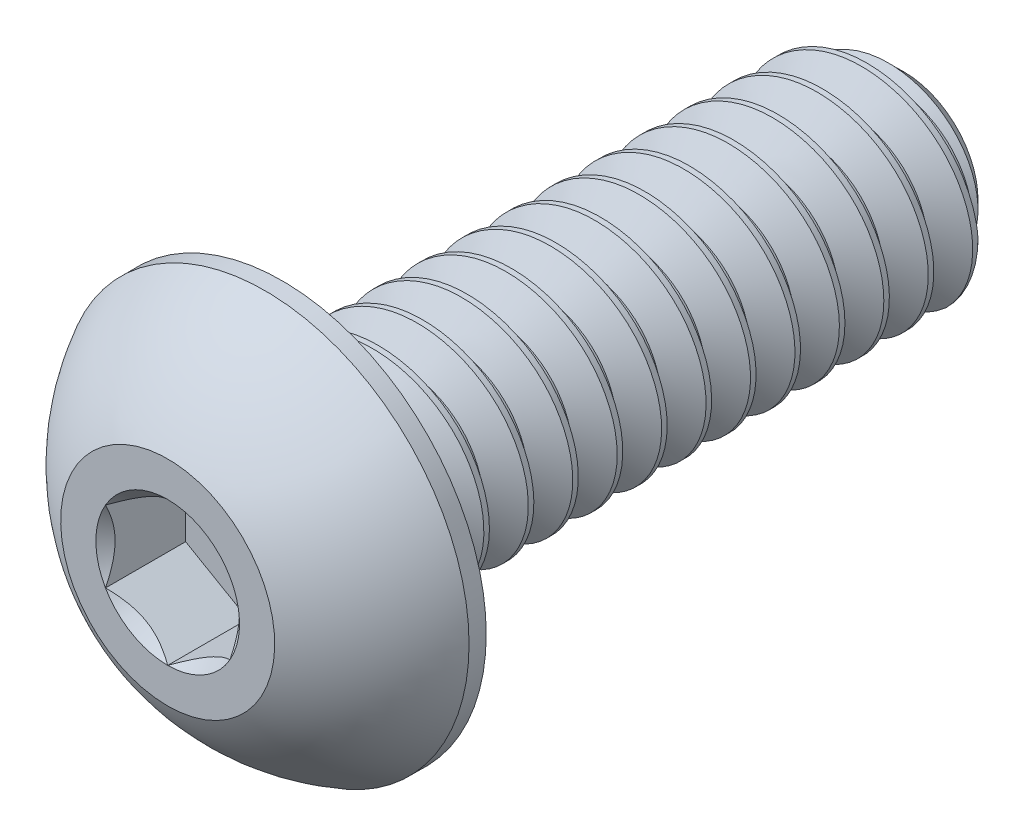
SolidWorks part; units mm, degrees
ref_plane "Front" through (0, 0, 0) normal (0, 0, 1) x (1, 0, 0)
ref_plane "Top" through (0, 0, 0) normal (0, 1, 0) x (1, 0, 0)
ref_plane "Right" through (0, 0, 0) normal (1, 0, 0) x (0, 0, -1)
sketch "Sketch1" plane through (0, 0, 0) normal (1, 0, 0) x (0, 0, -1)
  line L2 (1.1684, 1.0922) -> (7.5184, 1.0922)
  line L3 (7.5184, 1.0922) -> (7.5184, 0)
  line L4 (7.5184, 0) -> (1.1684, 0)
  line L6 (0.9931, 2.0828) -> (1.1684, 2.0828) construction
  line L7 (7.5184, 1.0922) -> (7.5184, -1.0922) construction
  line L8 (0, 0) -> (1.1684, 0) construction
  line L9 (1.1684, 2.0828) -> (1.1684, -2.0828) construction
  line L11 (1.1684, 1.0922) -> (1.1684, 0)
  line L13 (0, 0.635) -> (0, -0.635) construction
  line L14 (0, 0.635) -> (0, 1.0922) construction
  arc A3 (0, 1.0922) -> (0.9931, 2.0828) centre (2.08, 0) cw construction
  dimension "D1" = 0.1753
revolve "Revolve1" add sketch "Sketch1" angle 360 mid plane about L4
sketch "Sketch3" plane through (0, 0, -7.5184) normal (0, 0, -1) x (-1, 0, 0)
  circle A0 centre (0, 0) radius 1.0922
curve "Helix/Spiral1" pitch 0.4536 height 6.8036 radius 1.0922 centre (0, 0, -7.5184) axis (0, 0, 1) start towards (0, 1, 0)
sketch "Sketch2" plane through (0, 0, 0) normal (1, 0, 0) x (0, 0, -1)
  line L0 (7.5184, 1.0922) -> (7.9153, 1.0922)
  line L1 (7.9153, 1.0922) -> (7.7452, 0.7976)
  line L2 (7.7452, 0.7976) -> (7.6885, 0.7976)
  line L3 (7.6885, 0.7976) -> (7.5184, 1.0922)
  line L4 (7.6034, 0.9449) -> (7.8302, 0.9449) construction
  dimension "D1" = 60
  dimension "D2" = 0.0567
  dimension "D3" = 0.2268
chamfer "Chamfer1" distance 0.3402 angle 45 1 edges at (0, 1.0922, -7.5184)
sweep "Cut-Sweep1" cut profiles "Sketch2" path "Helix/Spiral1" align with end faces yes
sketch "Sketch7" plane through (0, 0, 0) normal (1, 0, 0) x (0, 0, -1)
  line L6 (0.9931, 2.0828) -> (1.1684, 2.0828) construction
  line L8 (0, 0) -> (1.1684, 0) construction
  line L11 (1.1684, 2.0828) -> (1.1684, -2.0828) construction
  line L12 (0.9931, 2.0828) -> (1.1684, 2.0828)
  line L13 (0, 0) -> (1.1684, 0)
  line L14 (0, 0.635) -> (0, -0.635) construction
  line L15 (1.1684, 2.0828) -> (1.1684, 0)
  line L16 (0, 1.0922) -> (0, 0)
  arc A2 (0.9931, 2.0828) -> (0, 1.0922) centre (2.08, 0) ccw construction
  arc A3 (0.9931, 2.0828) -> (0, 1.0922) centre (2.08, 0) ccw
revolve "Revolve2" add sketch "Sketch7" angle 360 mid plane about L13
sketch "Sketch5" plane through (0, 0, 0) normal (0, 0, 1) x (1, 0, 0)
  line L1 (0.635, -0.3666) -> (0.635, 0.3666)
  line L2 (0.635, 0.3666) -> (0, 0.7332)
  line L3 (0, 0.7332) -> (-0.635, 0.3666)
  line L4 (-0.635, 0.3666) -> (-0.635, -0.3666)
  line L5 (-0.635, -0.3666) -> (0, -0.7332)
  line L6 (0, -0.7332) -> (0.635, -0.3666)
  circle A0 centre (0, 0) radius 0.635 construction
extrude "Cut-Extrude2" cut sketch "Sketch5" against normal blind 0.8179
sketch "Sketch6" plane through (0, 0, 0) normal (0, 0, 1) x (1, 0, 0)
  circle A0 centre (0, 0) radius 0.7332
extrude "Cut-Extrude3" cut sketch "Sketch6" against normal blind 0.8179 draft 45
sketch "Sketch9" [suppressed] plane through (0, 0, -4.2164) normal (0, 0, 1) x (1, 0, 0)
  circle A2 centre (0, 0) radius 3.9687
extrude "Boss-Extrude2" [suppressed] add sketch "Sketch9" against normal offset from surface (9.525 mm away) 28.575 up to face at (0, 0.752, -7.5184)
sketch "Sketch10" plane through (0, 0, 0) normal (1, 0, 0) x (0, 0, -1)
  line L0 (7.5184, 1.0922) -> (7.5184, -1.0922) construction
  point P0 (6.838, -1.0922)
  dimension "D1" = 0.6804
equation "\"D3@Helix/Spiral1\" = \"Lg@Sketch1\" + \"D4@Helix/Spiral1\""
equation "\"D2@Sketch2\" = \"D4@Helix/Spiral1\" * .125"
equation "\"D3@Sketch2\" = \"D4@Helix/Spiral1\" * .5"
equation "\"D1@Chamfer1\" = \"D4@Helix/Spiral1\" * .75"
equation "\"D1@Cut-Extrude2\" = \"Head Ht@Sketch1\" * .7"
equation "\"D1@Sketch1\" = \"Head Ht@Sketch1\" * .15"
equation "\"D1@Sketch10\" = \"D4@Helix/Spiral1\" * 1.5"
equation "\"D1@Cut-Extrude3\" = \"D1@Cut-Extrude2\""
